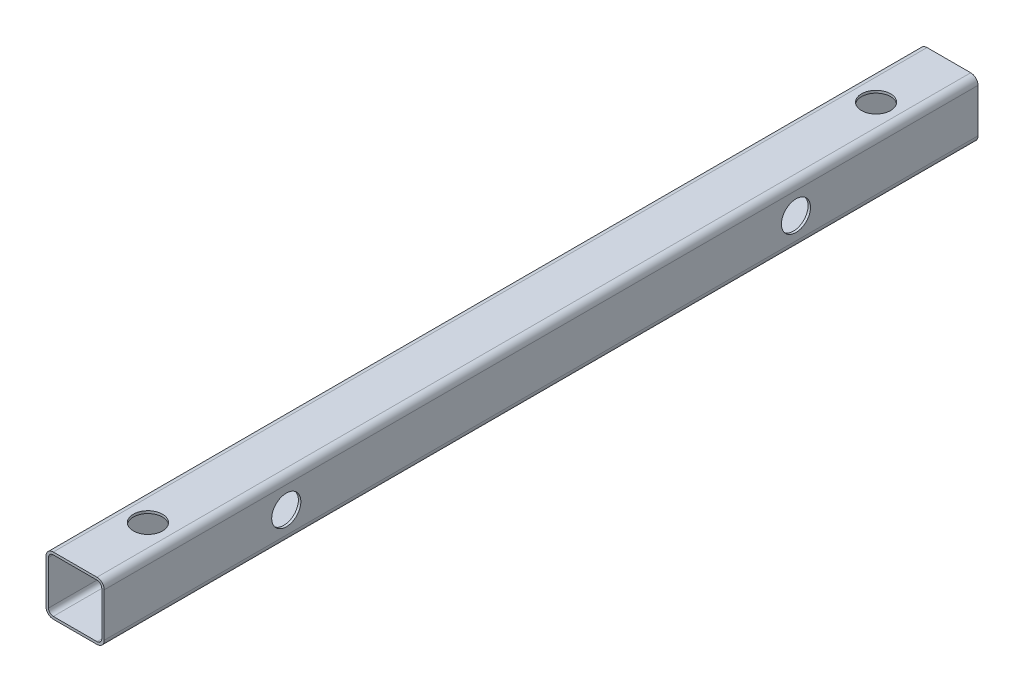
SolidWorks part; units mm, degrees
material "AISI 1010 Steel, hot rolled bar"
ref_plane "Front Plane" through (0, 0, 0) normal (0, 0, 1) x (1, 0, 0)
ref_plane "Top Plane" through (0, 0, 0) normal (0, 1, 0) x (1, 0, 0)
ref_plane "Right Plane" through (0, 0, 0) normal (1, 0, 0) x (0, 0, -1)
sketch "Sketch1" plane through (0, 0, 0) normal (0, 0, 1) x (1, 0, 0)
  line L0 (-6, 7.32) -> (6, 7.32)
  line L1 (-6, -8) -> (6, -8)
  line L2 (-8, -6) -> (-8, 6)
  line L3 (-6, 8) -> (6, 8)
  line L4 (8, -6) -> (8, 6)
  line L5 (-8, -8) -> (8, 8) construction
  line L6 (-8, 8) -> (8, -8) construction
  line L7 (7.32, -6) -> (7.32, 6)
  line L8 (-6, -7.32) -> (6, -7.32)
  line L9 (-7.32, -6) -> (-7.32, 6)
  arc A0 (-6, -8) -> (-8, -6) centre (-6, -6) cw
  arc A1 (6, -8) -> (8, -6) centre (6, -6) ccw
  arc A2 (6, 8) -> (8, 6) centre (6, 6) cw
  arc A3 (-8, 6) -> (-6, 8) centre (-6, 6) cw
  arc A4 (6, 7.32) -> (7.32, 6) centre (6, 6) cw
  arc A5 (6, -7.32) -> (7.32, -6) centre (6, -6) ccw
  arc A6 (-6, -7.32) -> (-7.32, -6) centre (-6, -6) cw
  arc A7 (-7.32, 6) -> (-6, 7.32) centre (-6, 6) cw
  point P0 (0, 0)
  dimension "D3" = 2
  dimension "D1" = 16
  dimension "D2" = 16
  dimension "D4" = 0.68
extrude "Boss-Extrude1" add sketch "Sketch1" along normal blind 120 and the other way blind 120
sketch "Sketch2" plane through (0, 8, 0) normal (0, 1, 0) x (1, 0, 0)
  line L0 (-6, 120) -> (-6, -120) construction
  line L1 (-8.8, 0) -> (8.8, 0) construction
  circle A0 centre (0, -100) radius 4
  circle A1 centre (0, 100) radius 4
  dimension "D1" = 8
  dimension "D2" = 100
  dimension "D3" = 6
sketch "Sketch3" plane through (8, 0, 0) normal (1, 0, 0) x (0, 0, -1)
  line L0 (120, 6) -> (-120, 6) construction
  line L1 (0, 8.8) -> (0, -8.8) construction
  circle A0 centre (-70, 0) radius 4
  circle A1 centre (70, 0) radius 4
  dimension "D1" = 8
  dimension "D2" = 70
  dimension "D3" = 6
extrude "Cut-Extrude1" cut sketch "Sketch2" against normal through all both and the other way through all
extrude "Cut-Extrude2" cut sketch "Sketch3" against normal through all both
